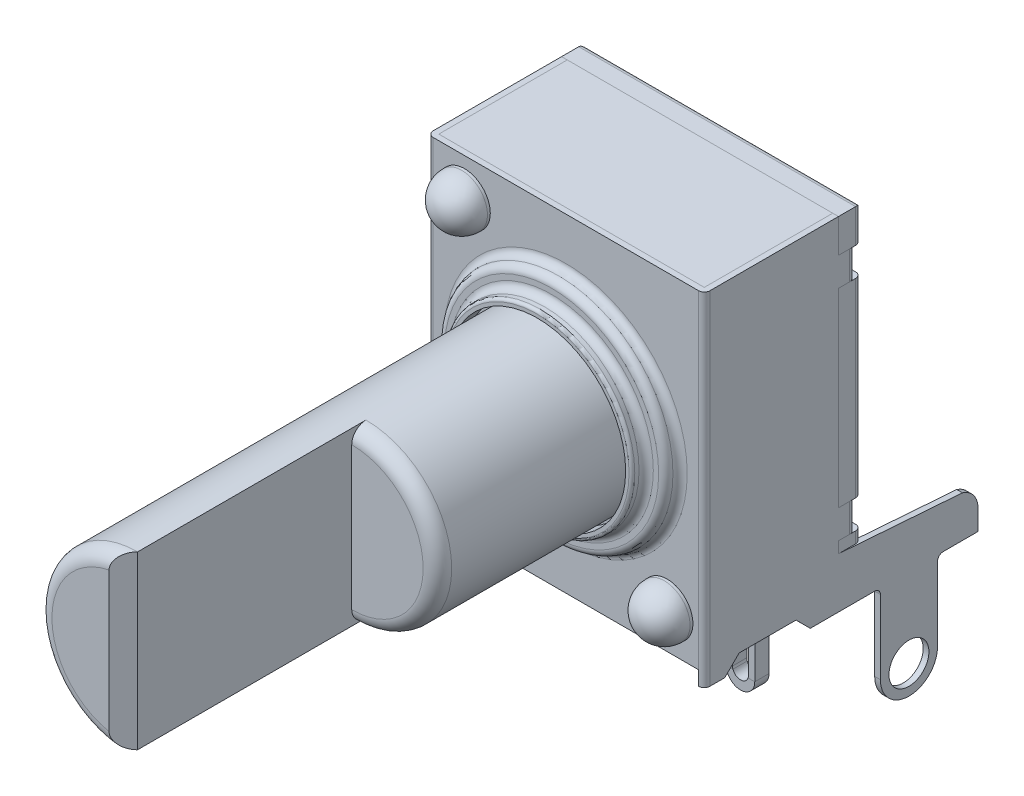
SolidWorks part; units mm, degrees
ref_plane "Спереди" through (0, 0, 0) normal (0, 0, 1) x (1, 0, 0)
ref_plane "Сверху" through (0, 0, 0) normal (0, 1, 0) x (1, 0, 0)
ref_plane "Справа" through (0, 0, 0) normal (1, 0, 0) x (0, 0, -1)
sketch "Эскиз1" plane through (0, 0, 0) normal (1, 0, 0) x (0, 0, -1)
  line L0 (-6.4501, 0) -> (-5.949, 0.5)
  line L1 (-1, 0) -> (1, 0) construction
  line L2 (-1, 0) -> (-1, -2.7855)
  line L3 (-6.9689, 12) -> (-2.4689, 12)
  line L4 (1, 0) -> (1, -2.7855)
  line L5 (-6.9689, 12) -> (-6.9689, 0)
  line L6 (-6.9689, 0) -> (-6.4501, 0)
  line L7 (-2.4689, 12) -> (-2.4689, 10.8216)
  line L8 (-5.949, 0.5) -> (-3.9549, 0.5)
  line L9 (-3.9549, 0.5) -> (-3.456, 0)
  line L10 (-2.448, 0) -> (-1, 0)
  line L11 (2.4188, 0.7798) -> (2.4188, 0)
  line L12 (-2.4689, 10.8216) -> (-2.0736, 10.8216)
  line L14 (-2.4689, 9.8216) -> (-2.0736, 9.8216)
  line L15 (-2.0736, 10.8216) -> (-2.0736, 9.8216)
  line L16 (-2.0736, 3.1632) -> (-2.4689, 3.1632)
  line L17 (-2.0736, 3.1632) -> (-2.0736, 2.1632)
  line L18 (-2.0736, 2.1632) -> (-2.4689, 2.1632)
  line L19 (-2.4689, 9.8216) -> (-2.4689, 3.1632)
  line L20 (2.4188, 0) -> (1, 0)
  line L21 (-2.4689, 1.768) -> (1.8753, 1.4468)
  line L22 (-3.456, 0) -> (-2.448, 0)
  line L23 (-2.4689, 2.1632) -> (-2.4689, 1.768)
  arc A0 (-1, -2.7855) -> (1, -2.7855) centre (0, -2.7855) ccw
  spline S0 degree 2 poles (1.8753, 1.4468) (2.35, 1.2797) (2.4188, 0.7798) knots 0 0 0 1 1 1
  dimension "D1" = 2
  dimension "D2" = 1
  dimension "D3" = 1
  dimension "D4" = 0.5
  dimension "D5" = 12
  dimension "D6" = 4.5
extrude "Бобышка-Вытянуть1" add sketch "Эскиз1" along normal mid plane 0.2
sketch "Эскиз2" plane through (0, 0, 6.9689) normal (0, 0, 1) x (1, 0, 0)
  line L1 (-0.1, 12) -> (4.7496, 12)
  line L2 (-0.1, 12) -> (-0.1, 0)
  line L3 (-0.1, 0) -> (4.7496, 0)
  line L4 (4.7496, 12) -> (4.7496, 0)
extrude "Бобышка-Вытянуть2" add sketch "Эскиз2" along normal blind 0.2
mirror "Зеркальное отражение1" about plane through (4.7496, 12, 7.1689) normal (-1, 0, 0) of bodies 102
sketch "Эскиз3" plane through (0, 0, 0) normal (0, -1, 0) x (1, 0, 0)
  line L1 (0.1, 6.9689) -> (9.3993, 6.9689)
  line L2 (0.1, 6.9689) -> (0.1, 7.5847)
  line L3 (0.1, 7.5847) -> (9.3993, 7.5847)
  line L4 (9.3993, 6.9689) -> (9.3993, 7.5847)
extrude "Вырез-Вытянуть1" cut sketch "Эскиз3" against normal blind 0.5
sketch "Эскиз5" plane through (9.3993, 0, 0) normal (-1, 0, 0) x (0, 0, 1)
  line L1 (6.9689, 0.5) -> (2.4689, 0.5)
  line L2 (6.9689, 0.5) -> (6.9689, 12)
  line L3 (6.9689, 12) -> (2.4689, 12)
  line L4 (2.4689, 0.5) -> (2.4689, 12)
extrude "Бобышка-Вытянуть3" add sketch "Эскиз5" along normal blind 9.3 separate body
sketch "Эскиз6" plane through (0, 0, 2.4689) normal (0, 0, -1) x (-1, 0, 0)
  line L0 (-0.1, 2.1632) -> (0.1, 2.1632)
  line L1 (-9.5993, 9.8216) -> (-9.3993, 9.8216)
  line L2 (-9.5993, 9.8216) -> (-9.5993, 3.1632)
  line L3 (-9.5993, 3.1632) -> (-9.3993, 3.1632)
  line L4 (0.1, 9.8216) -> (0.1, 3.1632)
  line L5 (-9.5993, 12) -> (0.1, 12)
  line L6 (-9.5993, 12) -> (-9.5993, 10.8216)
  line L7 (-9.5993, 10.8216) -> (-9.3993, 10.8216)
  line L8 (0.1, 12) -> (0.1, 10.8216)
  line L9 (-0.0993, 1.768) -> (0.1, 1.768)
  line L10 (-9.3993, 1.768) -> (-9.3993, 0.5)
  line L11 (-9.3993, 0.5) -> (-0.0993, 0.5)
  line L12 (-0.0993, 1.768) -> (-0.0993, 0.5)
  line L13 (-9.5993, 2.1632) -> (-9.3993, 2.1632)
  line L14 (-9.5993, 2.1632) -> (-9.5993, 1.768)
  line L15 (-9.5993, 1.768) -> (-9.3993, 1.768)
  line L16 (0.1, 2.1632) -> (0.1, 1.768)
  line L17 (-0.1, 9.8216) -> (0.1, 9.8216)
  line L18 (-9.3993, 3.1632) -> (-9.3993, 2.1632)
  line L19 (-0.1, 3.1632) -> (0.1, 3.1632)
  line L20 (-0.1, 3.1632) -> (-0.1, 2.1632)
  line L22 (-9.3993, 10.8216) -> (-9.3993, 9.8216)
  line L23 (-0.1, 10.8216) -> (0.1, 10.8216)
  line L24 (-0.1, 10.8216) -> (-0.1, 9.8216)
extrude "Бобышка-Вытянуть4" add sketch "Эскиз6" along normal blind 0.8 separate body
sketch "Эскиз7" plane through (0, 0, 1.6689) normal (0, 0, -1) x (-1, 0, 0)
  line L1 (-9.3993, 3.1632) -> (-8.3964, 3.1632)
  line L2 (-9.3993, 3.1632) -> (-9.3993, 2.1632)
  line L3 (-9.3993, 2.1632) -> (-8.3964, 2.1632)
  line L4 (-9.3993, 10.8216) -> (-8.3964, 10.8216)
  line L5 (-0.1, 3.1632) -> (-1.1029, 3.1632)
  line L6 (-0.1, 3.1632) -> (-0.1, 2.1632)
  line L7 (-0.1, 2.1632) -> (-1.1029, 2.1632)
  line L8 (-9.3993, 10.8216) -> (-9.3993, 9.8216)
  line L9 (-9.3993, 9.8216) -> (-8.3964, 9.8216)
  line L11 (-0.1, 10.8216) -> (-1.1029, 10.8216)
  line L12 (-0.1, 10.8216) -> (-0.1, 9.8216)
  line L13 (-0.1, 9.8216) -> (-1.1029, 9.8216)
  arc A0 (-8.3964, 2.1632) -> (-8.3964, 3.1632) centre (-8.3964, 2.6632) ccw
  arc A1 (-1.1029, 3.1632) -> (-1.1029, 2.1632) centre (-1.1029, 2.6632) ccw
  arc A2 (-8.3964, 9.8216) -> (-8.3964, 10.8216) centre (-8.3964, 10.3216) ccw
  arc A3 (-1.1029, 10.8216) -> (-1.1029, 9.8216) centre (-1.1029, 10.3216) ccw
extrude "Вырез-Вытянуть2" cut sketch "Эскиз7" against normal blind 0.4
sketch "Эскиз8" plane through (0, 0, 2.0736) normal (0, 0, -1) x (-1, 0, 0)
  line L1 (-9.5993, 3.1632) -> (-8.3964, 3.1632)
  line L2 (-9.5993, 3.1632) -> (-9.5993, 2.1632)
  line L3 (-9.5993, 2.1632) -> (-8.3964, 2.1632)
  line L4 (-9.5993, 10.8216) -> (-8.3964, 10.8216)
  line L5 (0.1, 3.1632) -> (-1.1029, 3.1632)
  line L6 (0.1, 3.1632) -> (0.1, 2.1632)
  line L7 (0.1, 2.1632) -> (-1.1029, 2.1632)
  line L8 (-9.5993, 10.8216) -> (-9.5993, 9.8216)
  line L9 (-9.5993, 9.8216) -> (-8.3964, 9.8216)
  line L11 (0.1, 10.8216) -> (-1.1029, 10.8216)
  line L12 (0.1, 10.8216) -> (0.1, 9.8216)
  line L13 (0.1, 9.8216) -> (-1.1029, 9.8216)
  arc A0 (-8.3964, 2.1632) -> (-8.3964, 3.1632) centre (-8.3964, 2.6632) ccw
  arc A1 (-1.1029, 3.1632) -> (-1.1029, 2.1632) centre (-1.1029, 2.6632) ccw
  arc A2 (-8.3964, 9.8216) -> (-8.3964, 10.8216) centre (-8.3964, 10.3216) ccw
  arc A3 (-1.1029, 10.8216) -> (-1.1029, 9.8216) centre (-1.1029, 10.3216) ccw
extrude "Бобышка-Вытянуть6" add sketch "Эскиз8" along normal blind 0.2 separate body
sketch "Эскиз9" plane through (0, 0.5, 0) normal (0, -1, 0) x (1, 0, 0)
  line L0 (-3.2974, 3.3) -> (13.0624, 3.3) construction
  line L1 (4.7493, 7.5468) -> (4.7493, -2.3222) construction
  line L2 (2.2493, 7.5468) -> (2.2493, -2.3222) construction
  line L3 (4.2481, 3.55) -> (5.2505, 3.55)
  line L4 (4.2481, 3.55) -> (4.2481, 3.05)
  line L5 (4.2481, 3.05) -> (5.2505, 3.05)
  line L6 (5.2505, 3.55) -> (5.2505, 3.05)
  line L7 (4.2481, 3.55) -> (5.2505, 3.05) construction
  line L8 (4.2481, 3.05) -> (5.2505, 3.55) construction
  line L9 (7.2493, 7.5468) -> (7.2493, -2.3222) construction
  line L11 (2.7476, 3.05) -> (1.751, 3.05)
  line L12 (2.7476, 3.05) -> (2.7476, 3.55)
  line L13 (2.7476, 3.55) -> (1.751, 3.55)
  line L14 (1.751, 3.05) -> (1.751, 3.55)
  line L15 (2.7476, 3.05) -> (1.751, 3.55) construction
  line L16 (2.7476, 3.55) -> (1.751, 3.05) construction
  line L17 (6.7502, 3.05) -> (7.7483, 3.05)
  line L18 (6.7502, 3.05) -> (6.7502, 3.55)
  line L19 (6.7502, 3.55) -> (7.7483, 3.55)
  line L20 (7.7483, 3.05) -> (7.7483, 3.55)
  line L21 (6.7502, 3.05) -> (7.7483, 3.55) construction
  line L22 (6.7502, 3.55) -> (7.7483, 3.05) construction
  point P2 (4.7493, 3.3)
  point P7 (4.7493, 3.3)
  point P16 (2.2493, 3.3)
  point P17 (7.2493, 3.3)
  point P18 (2.2493, 3.3)
  point P23 (7.2493, 3.3)
  dimension "D1" = 3.3
  dimension "D2" = 4.85
  dimension "D3" = 0.5
  dimension "D4" = 2.5
  dimension "D5" = 2.5
extrude "Бобышка-Вытянуть7" add sketch "Эскиз9" along normal blind 3 separate body
sketch "Эскиз11" plane through (0, 0, 3.55) normal (0, 0, 1) x (1, 0, 0)
  line L0 (7.7483, -2.5) -> (6.7502, -2.5)
  arc A0 (7.7483, -2.5) -> (6.7502, -2.5) centre (7.2493, -2.5) cw
extrude "Бобышка-Вытянуть8" add sketch "Эскиз11" against normal up to surface (0.5 mm away) up to face at (7.2493, -1, 3.05)
sketch "Эскиз12" plane through (0, 0, 3.05) normal (0, 0, -1) x (-1, 0, 0)
  line L0 (-5.2505, -2.5) -> (-4.2481, -2.5)
  line L1 (-2.7476, -2.5) -> (-1.751, -2.5)
  arc A0 (-5.2505, -2.5) -> (-4.2481, -2.5) centre (-4.7493, -2.5) ccw
  arc A1 (-2.7476, -2.5) -> (-1.751, -2.5) centre (-2.2493, -2.5) ccw
extrude "Бобышка-Вытянуть9" add sketch "Эскиз12" against normal up to surface (0.5 mm away) up to face at (4.7493, -1, 3.55)
sketch "Эскиз13" plane through (0, 0, 3.55) normal (0, 0, 1) x (1, 0, 0)
  line L0 (8.67, -1.7053) -> (1.5773, -1.7053) construction
  line L1 (2.2493, -1.0004) -> (2.2493, -2.4102) construction
  line L2 (2.5365, -1.0004) -> (2.5365, -2.4102)
  line L3 (1.962, -1.0004) -> (1.962, -2.4102)
  line L4 (4.7493, -1.0004) -> (4.7493, -2.4102) construction
  line L5 (5.0364, -1.0004) -> (5.0364, -2.4102)
  line L6 (4.4621, -1.0004) -> (4.4621, -2.4102)
  line L7 (7.2493, -1.0004) -> (7.2493, -2.4102) construction
  line L8 (7.5291, -1.0004) -> (7.5291, -2.4102)
  line L9 (6.9694, -1.0004) -> (6.9694, -2.4102)
  arc A0 (2.5365, -1.0004) -> (1.962, -1.0004) centre (2.2493, -1.0004) ccw
  arc A1 (1.962, -2.4102) -> (2.5365, -2.4102) centre (2.2493, -2.4102) ccw
  arc A2 (5.0364, -1.0004) -> (4.4621, -1.0004) centre (4.7493, -1.0004) ccw
  arc A3 (4.4621, -2.4102) -> (5.0364, -2.4102) centre (4.7493, -2.4102) ccw
  arc A4 (7.5291, -1.0004) -> (6.9694, -1.0004) centre (7.2493, -1.0004) ccw
  arc A5 (6.9694, -2.4102) -> (7.5291, -2.4102) centre (7.2493, -2.4102) ccw
  point P4 (2.2493, -1.7053)
  point P12 (4.7493, -1.7053)
  point P19 (7.2493, -1.7053)
extrude "Вырез-Вытянуть4" cut sketch "Эскиз13" against normal through all
sketch "Эскиз20" plane through (0, 0, 7.1689) normal (0, 0, 1) x (1, 0, 0)
  line L0 (-0.1, 12) -> (9.5993, 0.5) construction
  line L1 (-0.1, 0.5) -> (9.5993, 12) construction
  circle A0 centre (4.7496, 6.25) radius 4.002
extrude "Бобышка-Вытянуть13" add sketch "Эскиз20" along normal blind 0.5
sketch "Эскиз21" plane through (0, 0, 7.6689) normal (0, 0, 1) x (1, 0, 0)
  circle A0 centre (4.7496, 6.25) radius 3.3145
extrude "Бобышка-Вытянуть14" add sketch "Эскиз21" along normal blind 0.5
sketch "Эскиз22" plane through (0, 0, 8.1689) normal (0, 0, 1) x (1, 0, 0)
  circle A0 centre (4.7496, 6.25) radius 3.0958
extrude "Вырез-Вытянуть7" cut sketch "Эскиз22" against normal blind 0.5
sketch "Эскиз23" plane through (0, 0, 7.6689) normal (0, 0, 1) x (1, 0, 0)
  circle A0 centre (4.7496, 6.25) radius 3.0021
extrude "Бобышка-Вытянуть15" add sketch "Эскиз23" along normal blind 15 separate body
sketch "Эскиз24" plane through (0, 0, 22.6689) normal (0, 0, 1) x (1, 0, 0)
  line L1 (4.7496, 9.5645) -> (8.0642, 9.5645)
  line L2 (4.7496, 9.5645) -> (4.7496, 2.9355)
  line L3 (4.7496, 2.9355) -> (8.0642, 2.9355)
  line L4 (8.0642, 9.5645) -> (8.0642, 2.9355)
  circle A0 centre (4.7496, 6.25) radius 3.3145 construction
  circle A1 centre (4.7496, 6.25) radius 3.3145 construction
extrude "Вырез-Вытянуть8" cut sketch "Эскиз24" against normal blind 8
chamfer "Фаска2" distance 0.5 angle 45 1 edges at (4.7496, 6.25, 22.6689)
fillet "Скругление4" radius 0.5 2 edges at (7.7517, 6.25, 14.6689) (1.7476, 6.25, 22.6689)
fillet "Скругление5" radius 0.25 3 edges at (8.0642, 6.25, 7.6689) (8.7516, 6.25, 7.6689) (8.7516, 6.25, 7.1689)
fillet "Скругление6" radius 0.1 1 edges at (8.0642, 6.25, 8.1689)
fillet "Скругление7" radius 0.2 2 edges at (9.5993, 6, 7.1689) (-0.1, 6, 7.1689)
fillet "Скругление8" radius 0.2 8 edges at (4.7493, 0.5, 1.6689) (4.7496, 12, 1.6689) (9.5993, 1.9656, 1.6689) (9.5993, 6.4924, 1.6689) (9.5993, 11.4108, 1.6689) (-0.1, 1.9656, 1.6689) (-0.1, 11.4108, 1.6689) (-0.1, 6.4924, 1.6689)
sketch "Эскиз26" plane through (0, 0, 7.1689) normal (0, 0, 1) x (1, 0, 0)
  circle A0 centre (1.2, 10.7) radius 0.9029
  circle A1 centre (8.2993, 1.8) radius 0.9012
  dimension "D1" = 1.3
  dimension "D2" = 1.3
  dimension "D3" = 1.3
  dimension "D4" = 1.3
extrude "Бобышка-Вытянуть16" add sketch "Эскиз26" along normal blind 0.1 separate body
dome "Купол1" faces to dome 1 distance 0.9 reverse direction no elliptical dome yes face at (2.1029, 10.7, 7.2689) parameters "D1"=0.9
dome "Купол2" faces to dome 1 distance 0.9 reverse direction no elliptical dome yes face at (9.2005, 1.8, 7.2689) parameters "D1"=0.9
sketch "Эскиз27" plane through (-0.1, 0, 0) normal (-1, 0, 0) x (0, 0, 1)
  circle A0 centre (0, -2.7855) radius 0.7001
extrude "Вырез-Вытянуть9" cut sketch "Эскиз27" against normal through all
sketch "Эскиз28" plane through (0, 0, 1.6689) normal (0, 0, -1) x (-1, 0, 0)
  text T0 "RS09R" font "Times New Roman" height 1.5
extrude "Бобышка-Вытянуть17" add sketch "Эскиз28" along normal blind 0.15 separate body
sketch "Эскиз29" plane through (0, 0.5, 0) normal (0, -1, 0) x (1, 0, 0)
  line L0 (4.7496, 8.6362) -> (4.7496, 0.5747) construction
  line L1 (0.1, 6.9689) -> (9.3993, 6.9689) construction
  line L2 (2.3573, 6.9689) -> (7.0496, 6.9689)
  line L3 (2.3573, 6.9689) -> (2.3573, 5.6759)
  line L4 (2.3573, 5.6759) -> (7.0496, 5.6759)
  line L5 (7.0496, 6.9689) -> (7.0496, 5.6759)
  dimension "D1" = 2.3924
  dimension "D2" = 2.3
extrude "Вырез-Вытянуть10" cut sketch "Эскиз29" against normal blind 2.15
sketch "Эскиз30" plane through (0, 0, 1.6689) normal (0, 0, -1) x (-1, 0, 0)
  circle A0 centre (-4.7493, 5.0009) radius 2.3603
extrude "Бобышка-Вытянуть18" add sketch "Эскиз30" along normal blind 0.2 separate body
sketch "Эскиз31" plane through (0, 0, 1.4689) normal (0, 0, -1) x (-1, 0, 0)
  circle A0 centre (-4.7493, 5.0009) radius 1.7851
extrude "Вырез-Вытянуть11" cut sketch "Эскиз31" against normal blind 0.2
sketch "Эскиз32" plane through (0, 0, 1.6689) normal (0, 0, -1) x (-1, 0, 0)
  circle A0 centre (-4.7493, 5.0009) radius 0.2005
extrude "Вырез-Вытянуть12" cut sketch "Эскиз32" against normal blind 0.6
fillet "Скругление9" radius 0.2 1 edges at (9.5993, 10.3216, 1.8736)
fillet "Скругление10" radius 0.2 1 edges at (9.5993, 2.6632, 1.8736)
fillet "Скругление11" radius 0.2 1 edges at (-0.1, 10.3216, 1.8736)
fillet "Скругление12" radius 0.2 1 edges at (-0.1, 2.6632, 1.8736)
fillet "Скругление13" radius 0.2 4 edges at (9.4993, 0, -1) (0, 0, -1) (9.4993, 0, 1) (0, 0, 1)
